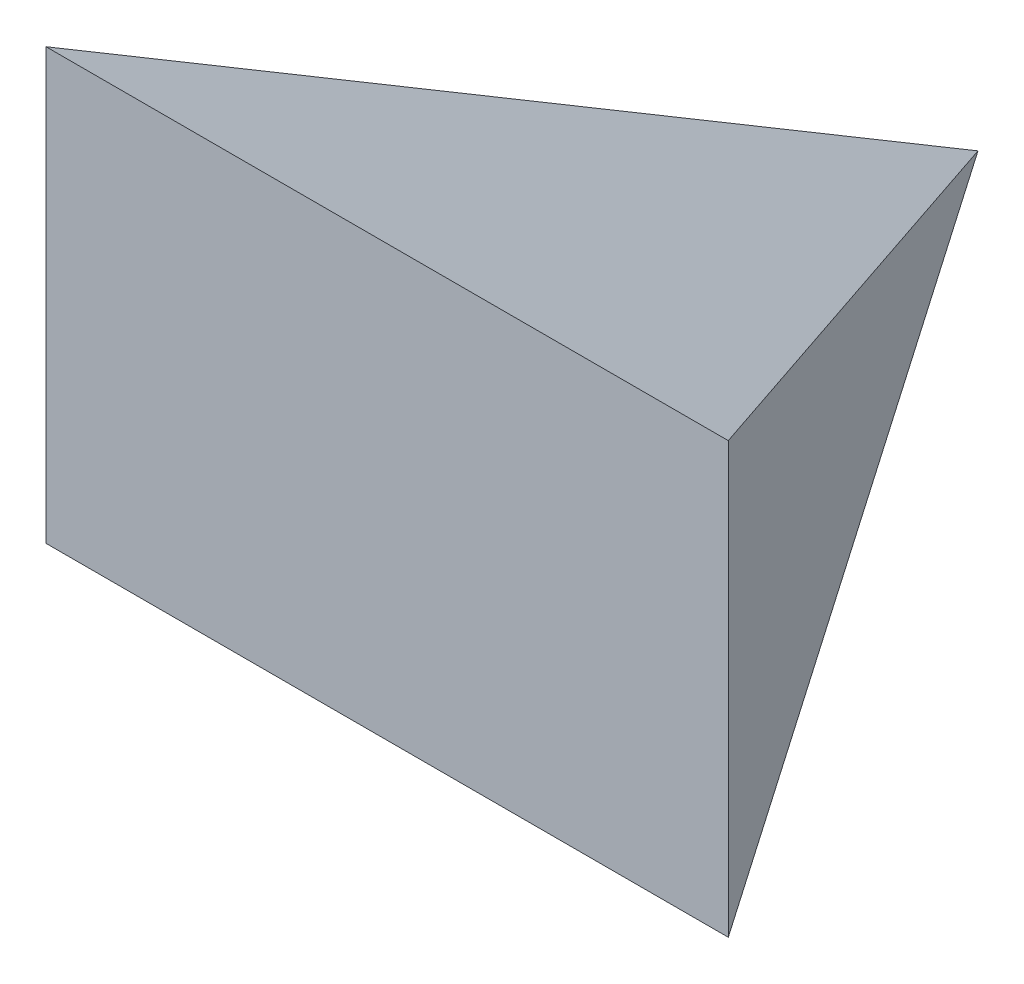
SolidWorks part; units mm, degrees
ref_plane "Front" through (0, 0, 0) normal (0, 0, 1) x (1, 0, 0)
ref_plane "Top" through (0, 0, 0) normal (0, 1, 0) x (1, 0, 0)
ref_plane "Right" through (0, 0, 0) normal (1, 0, 0) x (0, 0, -1)
sketch "Sketch1" plane through (0, 0, 0) normal (1, 0, 0) x (0, 0, -1)
  line L0 (0, 0) -> (-660.4, 240.3659)
  line L1 (0, 0) -> (-660.4, -240.3659)
  line L2 (0, 0) -> (-21.3134, 0) construction
  point P4 (0, 0)
  point P6 (0, 0)
  dimension "D1" = 40
  dimension "D2" = 660.4
sketch "Sketch2" plane through (0, 0, 0) normal (0, 1, 0) x (1, 0, 0)
  line L0 (-381.2821, -660.4) -> (0, 0)
  line L1 (0, 0) -> (381.2821, -660.4)
  line L2 (0, 0) -> (0, -21.3134) construction
  line L3 (0, 0) -> (0, -21.3134) construction
  line L4 (0, 0) -> (0, -660.4) construction
  point P9 (0, 0)
  point P10 (0, 0)
  dimension "D1" = 60
ref_plane "Plane1" through (0, 0, 660.4) normal (0, 0, 1) x (1, 0, 0)
sketch "Sketch3" plane through (0, 0, 660.4) normal (0, 0, 1) x (1, 0, 0)
  line L1 (381.2821, -240.3659) -> (-381.2821, -240.3659)
  line L2 (381.2821, -240.3659) -> (381.2821, 240.3659)
  line L3 (381.2821, 240.3659) -> (-381.2821, 240.3659)
  line L4 (-381.2821, -240.3659) -> (-381.2821, 240.3659)
  line L5 (381.2821, -240.3659) -> (-381.2821, 240.3659) construction
  line L6 (381.2821, 240.3659) -> (-381.2821, -240.3659) construction
  point P0 (0, 0)
sketch "Sketch4" plane through (0, 0, 0) normal (0, 0, 1) x (1, 0, 0)
  point P0 (0, 0)
loft "Loft1" add profiles "Sketch4", "Sketch3"
ref_axis "Axis1" through (0, 0, -80.9) along (0, 0, 1)
